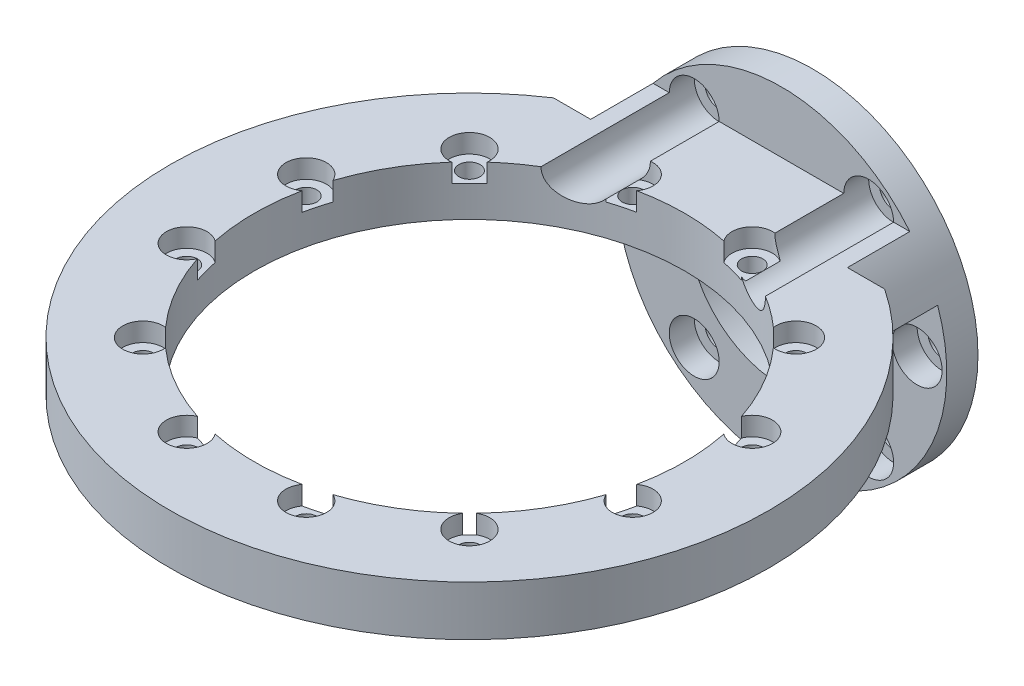
SolidWorks part; units mm, degrees
ref_plane "前视基准面" through (0, 0, 0) normal (0, 0, 1) x (1, 0, 0)
ref_plane "上视基准面" through (0, 0, 0) normal (0, 1, 0) x (1, 0, 0)
ref_plane "右视基准面" through (0, 0, 0) normal (1, 0, 0) x (0, 0, -1)
sketch "草图1" plane through (0, 0, 0) normal (0, 0, 1) x (1, 0, 0)
  circle A3 centre (0, 0) radius 26.5
extrude "凸台-拉伸1" add sketch "草图1" along normal blind 5
hole_wizard "M4 六角凹头盖的柱孔1" positions "3D草图2" profile "草图3" counterbore size "M4" standard "BSI" end condition through all
sketch3d "3D草图2"
  point P14 (-13.9806, 16.6615, 0)
  point P34 (-13.9806, 16.6615, 5)
  point P36 (13.9806, 16.6615, 5)
  point P38 (-21.75, 0, 5)
  point P40 (-13.9806, -16.6615, 5)
  point P42 (13.9806, -16.6615, 5)
  point P44 (21.75, 0, 5)
sketch "草图3" plane through (21.75, 0, 5) normal (1, 0, 0) x (0, -1, 0)
  line L0 (0, 0) -> (0, 5)
  line L1 (0, 5) -> (2.25, 5)
  line L3 (2.25, 5) -> (2.25, 4)
  line L4 (2.25, 4) -> (4, 4)
  line L5 (4, 4) -> (4, 0)
  line L7 (4, 0) -> (0, 0)
  line L11 (0, -6.35) -> (0, 107.95) construction
  dimension "通孔孔直径" = 4.5
  dimension "通孔孔深度" = 5
  dimension "柱形沉头孔直径" = 8
  dimension "柱形沉头孔深度" = 4
ref_plane "基准面1" through (0, 0, 5) normal (0, 0, 1) x (1, 0, 0)
sketch "参考" plane through (0, 0, 5) normal (0, 0, 1) x (1, 0, 0)
  line L12 (-20.7304, 8.7) -> (19.3146, 8.7) construction
ref_plane "基准面3" through (0, 8.7, 0) normal (0, -1, 0) x (1, 0, 0)
sketch "草图5" plane through (0, 8.7, 0) normal (0, -1, 0) x (1, 0, 0)
  line L0 (-26.5, 5) -> (-26.5, 14.9781)
  line L4 (26.5, 5) -> (26.5, 14.9781)
  line L9 (-26.5, 5) -> (26.5, 5)
  arc A4 (26.5, 14.9781) -> (-26.5, 14.9781) centre (0, 55) ccw
extrude "盘面" add sketch "草图5" against normal blind 8
sketch "草图6" plane through (0, 0, 5) normal (0, 0, 1) x (1, 0, 0)
  circle A0 centre (-13.9806, 16.6615) radius 4
  circle A1 centre (13.9806, 16.6615) radius 4
extrude "螺孔" cut sketch "草图6" along normal blind 22
sketch "草图8" plane through (0, 8.7, 0) normal (0, -1, 0) x (1, 0, 0)
  circle A1 centre (0, 55) radius 34.5
extrude "盘面切割" cut sketch "草图8" against normal through all
hole_wizard "M3 六角凹头盖的柱孔1" positions "3D草图3" profile "草图10" counterbore size "M3" standard "BSI" end condition through all
sketch3d "3D草图3"
  line L0 (0, 16.7, 55) -> (0, 8.7, 55) construction
  line L5 (0, 16.7, 55) -> (9.5763, 16.7, 19.2607)
  line L7 (0, 16.7, 55) -> (-9.5763, 16.7, 90.7393)
  line L11 (26.163, 16.7, 28.837) -> (0, 16.7, 55)
  line L17 (35.7393, 16.7, 45.4237) -> (0, 16.7, 55)
  line L19 (0, 16.7, 55) -> (35.7393, 16.7, 64.5763)
  line L21 (0, 16.7, 55) -> (26.6194, 16.7, 81.6194)
  line L22 (0, 16.7, 55) -> (-26.163, 16.7, 28.837)
  line L37 (0, 16.7, 55) -> (9.5763, 16.7, 90.7393)
  line L44 (-9.5763, 16.7, 19.2607) -> (0, 16.7, 55)
  line L54 (0, 16.7, 55) -> (-35.7393, 16.7, 45.4237)
  line L56 (0, 16.7, 55) -> (-26.163, 16.7, 81.163)
  line L68 (0, 16.7, 55) -> (-35.7393, 16.7, 64.5763)
  point P19 (9.5763, 16.7, 19.2607)
  point P34 (26.163, 16.7, 28.837)
  point P43 (35.7393, 16.7, 45.4237)
  point P46 (35.7393, 16.7, 64.5763)
  point P49 (26.6194, 16.7, 81.6194)
  point P169 (9.5763, 16.7, 90.7393)
  point P171 (-9.5763, 16.7, 90.7393)
  point P173 (-26.163, 16.7, 81.163)
  point P181 (-26.163, 16.7, 28.837)
  point P183 (-35.7393, 16.7, 45.4237)
  point P185 (-35.7393, 16.7, 64.5763)
  point P187 (-9.5763, 16.7, 19.2607)
sketch "草图10" plane through (-9.5763, 16.7, 19.2607) normal (1, 0, 0) x (0, 0, 1)
  line L0 (0, 0) -> (0, 43.2)
  line L1 (0, 43.2) -> (1.7, 43.2)
  line L3 (1.7, 43.2) -> (1.7, 3)
  line L4 (1.7, 3) -> (3.25, 3)
  line L5 (3.25, 3) -> (3.25, 0)
  line L7 (3.25, 0) -> (0, 0)
  line L11 (0, -6.35) -> (0, 107.95) construction
  dimension "通孔孔直径" = 3.4
  dimension "通孔孔深度" = 43.2
  dimension "柱形沉头孔直径" = 6.5
  dimension "柱形沉头孔深度" = 3
sketch "草图11" plane through (0, 0, 0) normal (0, 0, 1) x (1, 0, 0)
  line L0 (-25.0312, 8.7) -> (-29.0312, 8.7)
  line L1 (-29.15, 8.7) -> (29.15, 8.7) construction
  line L2 (-29.0312, 8.7) -> (-29.0312, 16.7)
  line L3 (48, 16.7) -> (-48, 16.7) construction
  line L4 (-29.0312, 16.7) -> (-20.5757, 16.7)
  line L6 (29.0312, 16.7) -> (20.5757, 16.7)
  line L7 (29.0312, 8.7) -> (29.0312, 16.7)
  line L8 (25.0312, 8.7) -> (29.0312, 8.7)
  arc A0 (-25.0312, 8.7) -> (25.0312, 8.7) centre (0, 0) ccw construction
  arc A1 (-25.0312, 8.7) -> (-20.5757, 16.7) centre (0, 0) cw
  arc A2 (25.0312, 8.7) -> (20.5757, 16.7) centre (0, 0) ccw
extrude "切除-拉伸1" cut sketch "草图11" along normal blind 15
sketch "草图12" plane through (0, 8.7, 0) normal (0, -1, 0) x (1, 0, 0)
  line L2 (39.2995, 79.0331) -> (30.6404, 73.9927)
  line L3 (40.2995, 32.8878) -> (31.6288, 37.8938)
  line L5 (25.4094, 16.6939) -> (19.8988, 25.0014)
  line L6 (39.2995, 31.1557) -> (30.6288, 36.1618)
  line L7 (31.6038, 72.2393) -> (40.2207, 77.2552)
  line L9 (-1, 96.0328) -> (-1, 90.9861)
  line L10 (1, 96.0328) -> (1, 101.0547)
  line L11 (1, 96.0328) -> (1, 90.9861)
  line L12 (-1, 96.0328) -> (-1, 101.0547)
  line L13 (-31.6038, 72.2393) -> (-40.2207, 77.2552)
  line L14 (-39.2995, 31.1557) -> (-30.6288, 36.1618)
  line L15 (-25.4094, 16.6939) -> (-19.8988, 25.0014)
  line L16 (-40.2995, 32.8878) -> (-31.6288, 37.8938)
  line L17 (-39.2995, 79.0331) -> (-30.6404, 73.9927)
  arc A9 (27.8489, 77.813) -> (22.813, 82.849) centre (26.6194, 81.6194) ccw
  arc A13 (12.9499, 88.5902) -> (5.5801, 90.5649) centre (9.5763, 90.7393) ccw
  arc A14 (33.5513, 42.0651) -> (35.5645, 49.4283) centre (35.7393, 45.4237) ccw
  arc A15 (35.5633, 60.5798) -> (33.59, 67.9502) centre (35.7393, 64.5763) ccw
  arc A16 (22.6075, 26.986) -> (27.9776, 32.4112) centre (26.163, 28.837) ccw
  arc A17 (12.9499, 88.5902) -> (22.813, 82.849) centre (0, 55) cw
  arc A18 (33.59, 67.9502) -> (31.6038, 72.2393) centre (0, 55) ccw
  arc A19 (35.5633, 60.5798) -> (35.5645, 49.4283) centre (0, 55) cw
  arc A20 (30.6288, 36.1618) -> (27.9776, 32.4112) centre (0, 55) cw
  arc A21 (22.6075, 26.986) -> (19.8988, 25.0014) centre (0, 55) cw
  arc A22 (5.5801, 90.5649) -> (1, 90.9861) centre (0, 55) ccw
  arc A23 (25.4094, 16.6939) -> (39.2995, 31.1557) centre (0, 55) ccw
  arc A24 (31.6288, 37.8938) -> (33.5513, 42.0651) centre (0, 55) ccw
  arc A25 (40.2995, 32.8878) -> (40.2207, 77.2552) centre (0, 55) ccw
  arc A26 (39.2995, 79.0331) -> (1, 101.0547) centre (0, 55) ccw
  arc A27 (30.6404, 73.9927) -> (27.8992, 77.8296) centre (0, 55) ccw
  arc A28 (-30.6404, 73.9927) -> (-27.8992, 77.8296) centre (0, 55) cw
  arc A29 (-39.2995, 79.0331) -> (-1, 101.0547) centre (0, 55) cw
  arc A30 (-40.2995, 32.8878) -> (-40.2207, 77.2552) centre (0, 55) cw
  arc A31 (-31.6288, 37.8938) -> (-33.5513, 42.0651) centre (0, 55) cw
  arc A32 (-25.4094, 16.6939) -> (-39.2995, 31.1557) centre (0, 55) cw
  arc A33 (-5.5801, 90.5649) -> (-1, 90.9861) centre (0, 55) cw
  arc A34 (-22.6075, 26.986) -> (-19.8988, 25.0014) centre (0, 55) ccw
  arc A35 (-30.6288, 36.1618) -> (-27.9776, 32.4112) centre (0, 55) ccw
  arc A36 (-35.5633, 60.5798) -> (-35.5645, 49.4283) centre (0, 55) ccw
  arc A37 (-33.59, 67.9502) -> (-31.6038, 72.2393) centre (0, 55) cw
  arc A38 (-12.9499, 88.5902) -> (-22.813, 82.849) centre (0, 55) ccw
  arc A39 (-22.6075, 26.986) -> (-27.9776, 32.4112) centre (-26.163, 28.837) cw
  arc A40 (-35.5633, 60.5798) -> (-33.59, 67.9502) centre (-35.7393, 64.5763) cw
  arc A41 (-33.5513, 42.0651) -> (-35.5645, 49.4283) centre (-35.7393, 45.4237) cw
  arc A42 (-12.9499, 88.5902) -> (-5.5801, 90.5649) centre (-9.5763, 90.7393) cw
  arc A43 (-27.8489, 77.813) -> (-22.813, 82.849) centre (-26.6194, 81.6194) cw
extrude "切除-拉伸2" cut sketch "草图12" against normal blind 5 contours A27 L2 A26 L10 L11 A22 A13 A17 A9 | L3 A25 L7 A18 A15 A19 A14 A24 | L5 A23 L6 A20 A16 A21 | A28 A43 A38 A42 A33 L9 L12 A29 L17 | A31 A41 A36 A40 A37 L13 A30 L16 | A34 A39 A35 L14 A32 L15 region at (19.8462, 8.7, 89.8632) region at (40.0107, 8.7, 55.079) region at (30.014, 8.7, 26.342) region at (-19.8462, 8.7, 89.8632) region at (-40.0107, 8.7, 55.079) region at (-30.014, 8.7, 26.342)
sketch "草图13" plane through (0, 0, 5) normal (0, 0, 1) x (1, 0, 0)
  line L0 (-20.7304, 8.7) -> (19.3146, 8.7) construction
  line L1 (-12.2192, 8.7) -> (12.2192, 8.7)
  arc A1 (-12.2192, 8.7) -> (12.2192, 8.7) centre (0, 0) ccw
extrude "切除-拉伸3" cut sketch "草图13" against normal blind 10
